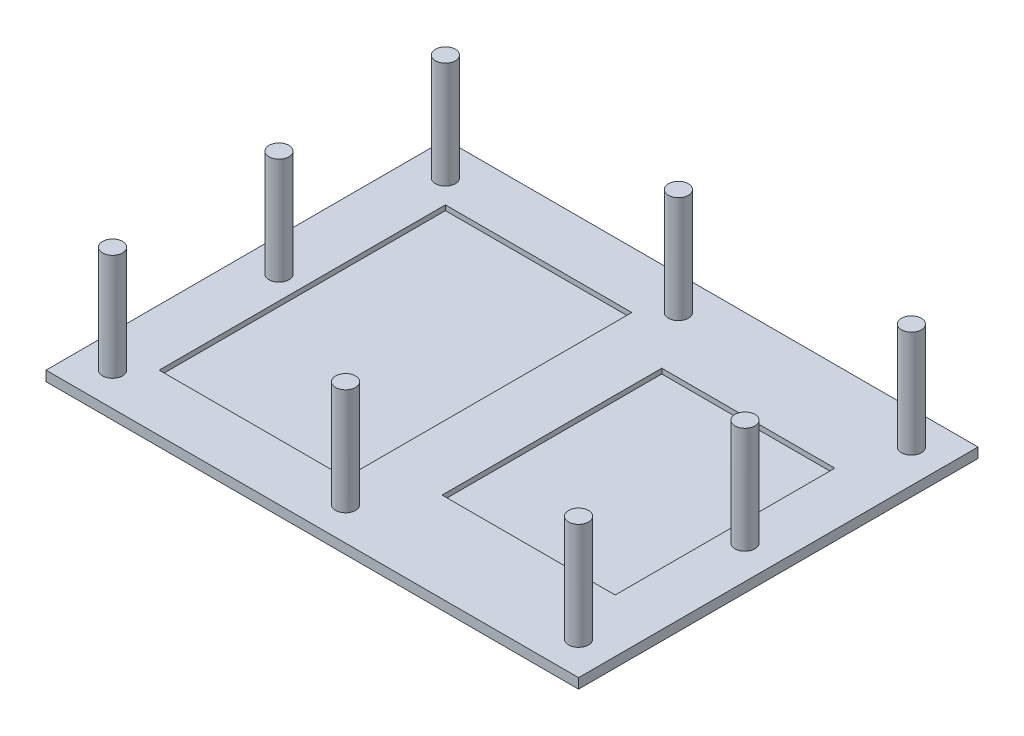
SolidWorks part; units mm, degrees
ref_plane "Front Plane" through (0, 0, 0) normal (0, 0, 1) x (1, 0, 0)
ref_plane "Top Plane" through (0, 0, 0) normal (0, 1, 0) x (1, 0, 0)
ref_plane "Right Plane" through (0, 0, 0) normal (1, 0, 0) x (0, 0, -1)
sketch "Sketch1" plane through (0, 0, 0) normal (0, 1, 0) x (1, 0, 0)
  line L1 (-80, -60) -> (80, -60)
  line L2 (-80, -60) -> (-80, 60)
  line L3 (-80, 60) -> (80, 60)
  line L4 (80, -60) -> (80, 60)
  line L5 (-80, -60) -> (80, 60) construction
  line L6 (-80, 60) -> (80, -60) construction
  point P0 (0, 0)
  dimension "D1" = 120
  dimension "D2" = 160
extrude "Boss-Extrude1" add sketch "Sketch1" along normal blind 3
sketch "Sketch2" plane through (0, 3, 0) normal (0, 1, 0) x (1, 0, 0)
  line L0 (0, 60) -> (0, 50) construction
  line L1 (80, 60) -> (-80, 60) construction
  line L2 (-80, -60) -> (80, -60) construction
  line L3 (80, 0) -> (70, 0) construction
  line L4 (80, -60) -> (80, 60) construction
  line L5 (-80, 0) -> (-70, 0) construction
  line L6 (-80, 60) -> (-80, -60) construction
  line L7 (-80, 60) -> (-70, 60) construction
  line L8 (-70, 60) -> (-70, 50) construction
  line L9 (-80, -60) -> (-70, -60) construction
  line L10 (-70, -60) -> (-70, -50) construction
  line L11 (80, 60) -> (70, 60) construction
  line L12 (70, 60) -> (70, 50) construction
  line L13 (80, -60) -> (70, -60) construction
  line L14 (70, -60) -> (70, -50) construction
  line L15 (0, -60) -> (0, -50) construction
  circle A0 centre (-70, 50) radius 3
  circle A1 centre (0, 50) radius 3
  circle A2 centre (70, 50) radius 3
  circle A3 centre (-70, 0) radius 3
  circle A4 centre (70, 0) radius 3
  circle A5 centre (-70, -50) radius 3
  circle A6 centre (0, -50) radius 3
  circle A7 centre (70, -50) radius 3
  dimension "D13" = 6
  dimension "D14" = 6
  dimension "D15" = 6
  dimension "D16" = 6
  dimension "D17" = 6
  dimension "D18" = 6
  dimension "D19" = 6
  dimension "D20" = 6
  dimension "D1" = 10
  dimension "D2" = 10
  dimension "D3" = 10
  dimension "D4" = 10
  dimension "D5" = 10
  dimension "D6" = 10
  dimension "D7" = 10
  dimension "D8" = 10
  dimension "D9" = 10
  dimension "D10" = 10
  dimension "D11" = 10
  dimension "D12" = 10
extrude "Boss-Extrude2" add sketch "Sketch2" along normal blind 32
sketch "Sketch3" plane through (0, 3, 0) normal (0, 1, 0) x (1, 0, 0)
  line L0 (80, 60) -> (-80, 60) construction
  line L1 (-63, -43) -> (-7, -43)
  line L2 (-63, -43) -> (-63, 43)
  line L3 (-63, 43) -> (-7, 43)
  line L4 (-7, -43) -> (-7, 43)
  line L6 (-80, 60) -> (-80, -60) construction
  dimension "D1" = 86
  dimension "D2" = 56
  dimension "D3" = 17
  dimension "D4" = 17
extrude "Cut-Extrude1" cut sketch "Sketch3" against normal blind 1.5 contours L2 L3 L4 L1
sketch "Sketch5" plane through (0, 3, 0) normal (0, 1, 0) x (1, 0, 0)
  line L0 (80, -60) -> (80, 60) construction
  line L1 (12, 33) -> (64, 33)
  line L2 (12, 33) -> (12, -33)
  line L3 (12, -33) -> (64, -33)
  line L4 (64, 33) -> (64, -33)
  line L5 (80, 60) -> (-80, 60) construction
  dimension "D1" = 52
  dimension "D2" = 66
  dimension "D3" = 16
  dimension "D4" = 27
extrude "Cut-Extrude2" cut sketch "Sketch5" against normal blind 1.5
